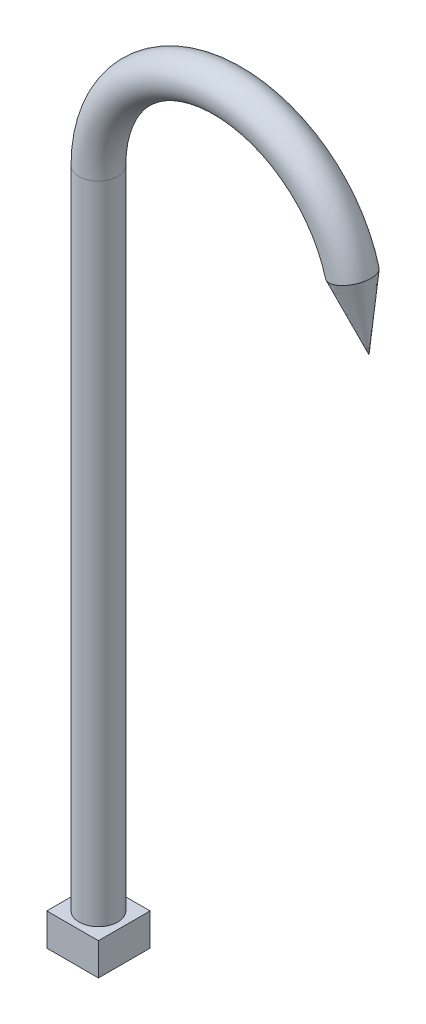
SolidWorks part; units mm, degrees
ref_plane "Front Plane" through (0, 0, 0) normal (0, 0, 1) x (1, 0, 0)
ref_plane "Top Plane" through (0, 0, 0) normal (0, 1, 0) x (1, 0, 0)
ref_plane "Right Plane" through (0, 0, 0) normal (1, 0, 0) x (0, 0, -1)
sketch "Sketch1" plane through (0, 0, 0) normal (0, 1, 0) x (1, 0, 0)
  line L1 (-4, -4) -> (4, -4)
  line L2 (-4, -4) -> (-4, 4)
  line L3 (-4, 4) -> (4, 4)
  line L4 (4, -4) -> (4, 4)
  line L5 (-4, -4) -> (4, 4) construction
  line L6 (-4, 4) -> (4, -4) construction
  point P0 (0, 0)
  dimension "D1" = 8
  dimension "D2" = 8
extrude "Boss-Extrude1" add sketch "Sketch1" along normal blind 5
sketch "Sketch2" plane through (0, 0, 0) normal (0, 0, 1) x (1, 0, 0)
  line L0 (0, 5) -> (0, 105)
  line L1 (-4, 5) -> (4, 5) construction
  line L2 (39.3185, 110.1764) -> (41.9067, 100.5171)
  arc A0 (0, 105) -> (39.3185, 110.1764) centre (20, 105) cw
sketch "Sketch3" plane through (0, 5, 0) normal (0, 1, 0) x (1, 0, 0)
  circle A0 centre (0, 0) radius 3
sweep "Sweep1" add profiles "Sketch3" path "Sketch2"
chamfer "Chamfer1" distance 10 distance2 3 1 edges at (41.9067, 100.5171, 3) first distance on face at (39.3185, 110.1764, 3)
